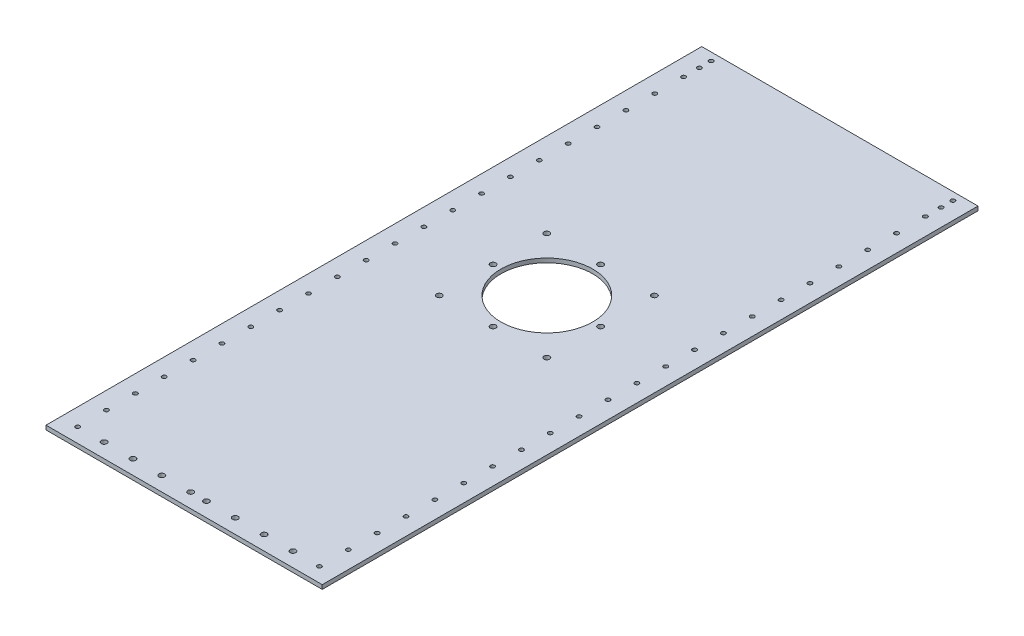
SolidWorks part; units mm, degrees
ref_plane "Front Plane" through (0, 0, 0) normal (0, 0, 1) x (1, 0, 0)
ref_plane "Top Plane" through (0, 0, 0) normal (0, 1, 0) x (1, 0, 0)
ref_plane "Right Plane" through (0, 0, 0) normal (1, 0, 0) x (0, 0, -1)
sketch "Sketch1" plane through (0, 0, 0) normal (0, 1, 0) x (1, 0, 0)
  line L0 (0, 250) -> (0, -250) construction
  line L1 (-105.305, -250) -> (105.305, -250)
  line L2 (-105.305, -250) -> (-105.305, 250)
  line L3 (-105.305, 250) -> (105.305, 250)
  line L4 (105.305, -250) -> (105.305, 250)
  line L5 (-105.305, -250) -> (105.305, 250) construction
  line L6 (-105.305, 250) -> (105.305, -250) construction
  line L7 (-105.305, 26.549) -> (105.305, 26.549) construction
  circle A0 centre (92.18, 244) radius 1.6
  circle A1 centre (92.18, 235) radius 1.6
  circle A2 centre (92.18, 223) radius 1.6
  circle A3 centre (92.18, 201) radius 1.6
  circle A4 centre (92.18, 179) radius 1.6
  circle A5 centre (92.18, 157) radius 1.6
  circle A6 centre (92.18, 135) radius 1.6
  circle A7 centre (92.18, 113) radius 1.6
  circle A8 centre (92.18, 91) radius 1.6
  circle A9 centre (92.18, 69) radius 1.6
  circle A10 centre (92.18, 47) radius 1.6
  circle A11 centre (92.18, 25) radius 1.6
  circle A12 centre (92.18, 3) radius 1.6
  circle A13 centre (92.18, -19) radius 1.6
  circle A14 centre (92.18, -41) radius 1.6
  circle A15 centre (92.18, -63) radius 1.6
  circle A16 centre (92.18, -85) radius 1.6
  circle A17 centre (92.18, -107) radius 1.6
  circle A18 centre (92.18, -129) radius 1.6
  circle A19 centre (92.18, -151) radius 1.6
  circle A20 centre (92.18, -173) radius 1.6
  circle A21 centre (92.18, -195) radius 1.6
  circle A22 centre (92.18, -217) radius 1.6
  circle A23 centre (92.18, -239) radius 1.6
  circle A24 centre (-92.18, 69) radius 1.6
  circle A25 centre (-92.18, 91) radius 1.6
  circle A26 centre (-92.18, 113) radius 1.6
  circle A27 centre (-92.18, 135) radius 1.6
  circle A28 centre (-92.18, 157) radius 1.6
  circle A29 centre (-92.18, 179) radius 1.6
  circle A30 centre (-92.18, 201) radius 1.6
  circle A31 centre (-92.18, 223) radius 1.6
  circle A32 centre (-92.18, 235) radius 1.6
  circle A33 centre (-92.18, -239) radius 1.6
  circle A34 centre (-92.18, -217) radius 1.6
  circle A35 centre (-92.18, -195) radius 1.6
  circle A36 centre (-92.18, -173) radius 1.6
  circle A37 centre (-92.18, -151) radius 1.6
  circle A38 centre (-92.18, -129) radius 1.6
  circle A39 centre (-92.18, -107) radius 1.6
  circle A40 centre (-92.18, -85) radius 1.6
  circle A41 centre (-92.18, -63) radius 1.6
  circle A42 centre (-92.18, -41) radius 1.6
  circle A43 centre (-92.18, -19) radius 1.6
  circle A44 centre (-92.18, 3) radius 1.6
  circle A45 centre (-92.18, 25) radius 1.6
  circle A46 centre (-92.18, 47) radius 1.6
  circle A47 centre (-92.18, 244) radius 1.6
  circle A48 centre (6, -239) radius 2.125
  circle A49 centre (28, -239) radius 2.125
  circle A50 centre (50, -239) radius 2.125
  circle A51 centre (72, -239) radius 2.125
  circle A220 centre (-72, -239) radius 2.125
  circle A221 centre (-50, -239) radius 2.125
  circle A222 centre (-28, -239) radius 2.125
  circle A223 centre (-6, -239) radius 2.125
  circle A224 centre (28, -217) radius 2.125 [skipped]
  circle A225 centre (50, -217) radius 2.125 [skipped]
  circle A226 centre (28, -195) radius 2.125 [skipped]
  circle A227 centre (50, -195) radius 2.125 [skipped]
  circle A228 centre (28, -173) radius 2.125 [skipped]
  circle A229 centre (50, -173) radius 2.125 [skipped]
  circle A230 centre (28, -151) radius 2.125 [skipped]
  circle A231 centre (50, -151) radius 2.125 [skipped]
  circle A232 centre (28, -129) radius 2.125 [skipped]
  circle A233 centre (50, -129) radius 2.125 [skipped]
  circle A234 centre (28, -107) radius 2.125 [skipped]
  circle A235 centre (50, -107) radius 2.125 [skipped]
  circle A236 centre (28, -85) radius 2.125 [skipped]
  circle A237 centre (50, -85) radius 2.125 [skipped]
  circle A238 centre (28, -63) radius 2.125 [skipped]
  circle A239 centre (50, -63) radius 2.125 [skipped]
  circle A240 centre (28, -41) radius 2.125 [skipped]
  circle A241 centre (50, -41) radius 2.125 [skipped]
  circle A242 centre (28, -19) radius 2.125 [skipped]
  circle A243 centre (50, -19) radius 2.125 [skipped]
  circle A244 centre (28, 3) radius 2.125 [skipped]
  circle A245 centre (50, 3) radius 2.125 [skipped]
  circle A246 centre (28, 25) radius 2.125 [skipped]
  circle A247 centre (50, 25) radius 2.125 [skipped]
  circle A248 centre (28, 47) radius 2.125 [skipped]
  circle A249 centre (50, 47) radius 2.125 [skipped]
  circle A250 centre (28, 69) radius 2.125 [skipped]
  circle A251 centre (50, 69) radius 2.125 [skipped]
  circle A252 centre (28, 91) radius 2.125 [skipped]
  circle A253 centre (50, 91) radius 2.125 [skipped]
  circle A254 centre (28, 113) radius 2.125 [skipped]
  circle A255 centre (50, 113) radius 2.125 [skipped]
  circle A256 centre (28, 135) radius 2.125 [skipped]
  circle A257 centre (50, 135) radius 2.125 [skipped]
  circle A258 centre (28, 157) radius 2.125 [skipped]
  circle A259 centre (50, 157) radius 2.125 [skipped]
  circle A260 centre (28, 179) radius 2.125 [skipped]
  circle A261 centre (50, 179) radius 2.125 [skipped]
  circle A262 centre (28, 201) radius 2.125 [skipped]
  circle A263 centre (50, 201) radius 2.125 [skipped]
  circle A264 centre (28, 223) radius 2.125 [skipped]
  circle A265 centre (50, 223) radius 2.125 [skipped]
  circle A266 centre (6, -217) radius 2.125 [skipped]
  circle A267 centre (6, -195) radius 2.125 [skipped]
  circle A268 centre (6, -173) radius 2.125 [skipped]
  circle A269 centre (6, -151) radius 2.125 [skipped]
  circle A270 centre (6, -129) radius 2.125 [skipped]
  circle A271 centre (6, -107) radius 2.125 [skipped]
  circle A272 centre (6, -85) radius 2.125 [skipped]
  circle A273 centre (6, -63) radius 2.125 [skipped]
  circle A274 centre (6, -41) radius 2.125 [skipped]
  circle A275 centre (6, -19) radius 2.125 [skipped]
  circle A276 centre (6, 3) radius 2.125 [skipped]
  circle A277 centre (6, 25) radius 2.125 [skipped]
  circle A278 centre (6, 47) radius 2.125 [skipped]
  circle A279 centre (6, 69) radius 2.125 [skipped]
  circle A280 centre (6, 91) radius 2.125 [skipped]
  circle A281 centre (6, 113) radius 2.125 [skipped]
  circle A282 centre (6, 135) radius 2.125 [skipped]
  circle A283 centre (6, 157) radius 2.125 [skipped]
  circle A284 centre (6, 179) radius 2.125 [skipped]
  circle A285 centre (6, 201) radius 2.125 [skipped]
  circle A286 centre (6, 223) radius 2.125 [skipped]
  circle A287 centre (72, -217) radius 2.125 [skipped]
  circle A288 centre (72, -195) radius 2.125 [skipped]
  circle A289 centre (72, -173) radius 2.125 [skipped]
  circle A290 centre (72, -151) radius 2.125 [skipped]
  circle A291 centre (72, -129) radius 2.125 [skipped]
  circle A292 centre (72, -107) radius 2.125 [skipped]
  circle A293 centre (72, -85) radius 2.125 [skipped]
  circle A294 centre (72, -63) radius 2.125 [skipped]
  circle A295 centre (72, -41) radius 2.125 [skipped]
  circle A296 centre (72, -19) radius 2.125 [skipped]
  circle A297 centre (72, 3) radius 2.125 [skipped]
  circle A298 centre (72, 25) radius 2.125 [skipped]
  circle A299 centre (72, 47) radius 2.125 [skipped]
  circle A300 centre (72, 69) radius 2.125 [skipped]
  circle A301 centre (72, 91) radius 2.125 [skipped]
  circle A302 centre (72, 113) radius 2.125 [skipped]
  circle A303 centre (72, 135) radius 2.125 [skipped]
  circle A304 centre (72, 157) radius 2.125 [skipped]
  circle A305 centre (72, 179) radius 2.125 [skipped]
  circle A306 centre (72, 201) radius 2.125 [skipped]
  circle A307 centre (72, 223) radius 2.125 [skipped]
  circle A310 centre (0, 26.549) radius 35
  circle A311 centre (41, 26.549) radius 2.125
  circle A312 centre (0, 67.549) radius 2.125
  circle A313 centre (41, 67.549) radius 2.125
  circle A314 centre (-41, 26.549) radius 2.125
  circle A315 centre (-41, 67.549) radius 2.125
  circle A316 centre (41, -14.451) radius 2.125
  circle A317 centre (0, -14.451) radius 2.125
  circle A318 centre (-41, -14.451) radius 2.125
  dimension "D3" = 3.2
  dimension "D8" = 3.2
  dimension "D9" = 3.2
  dimension "D11" = 4.25
  dimension "D16" = 70
  dimension "D17" = 4.25
  dimension "D19" = 4.25
  dimension "D21" = 4.25
  dimension "D2" = 500
  dimension "D4" = 13.125
  dimension "D5" = 6
  dimension "D6" = 9
  dimension "D7" = 12
  dimension "D12" = 6
  dimension "D15" = 276.549
  dimension "D18" = 41
  dimension "D20" = 41
  dimension "D22" = 41
  dimension "D23" = 41
  dimension "D10" = 22
  dimension "D13" = 4
  dimension "D14" = 22
extrude "Boss-Extrude1" add sketch "Sketch1" along normal blind 3.175
equation "\"m3\"=3.2"
equation "\"D3@Sketch1\"=\"m3\""
equation "\"D8@Sketch1\"=\"m3\""
equation "\"D9@Sketch1\"=\"m3\""
